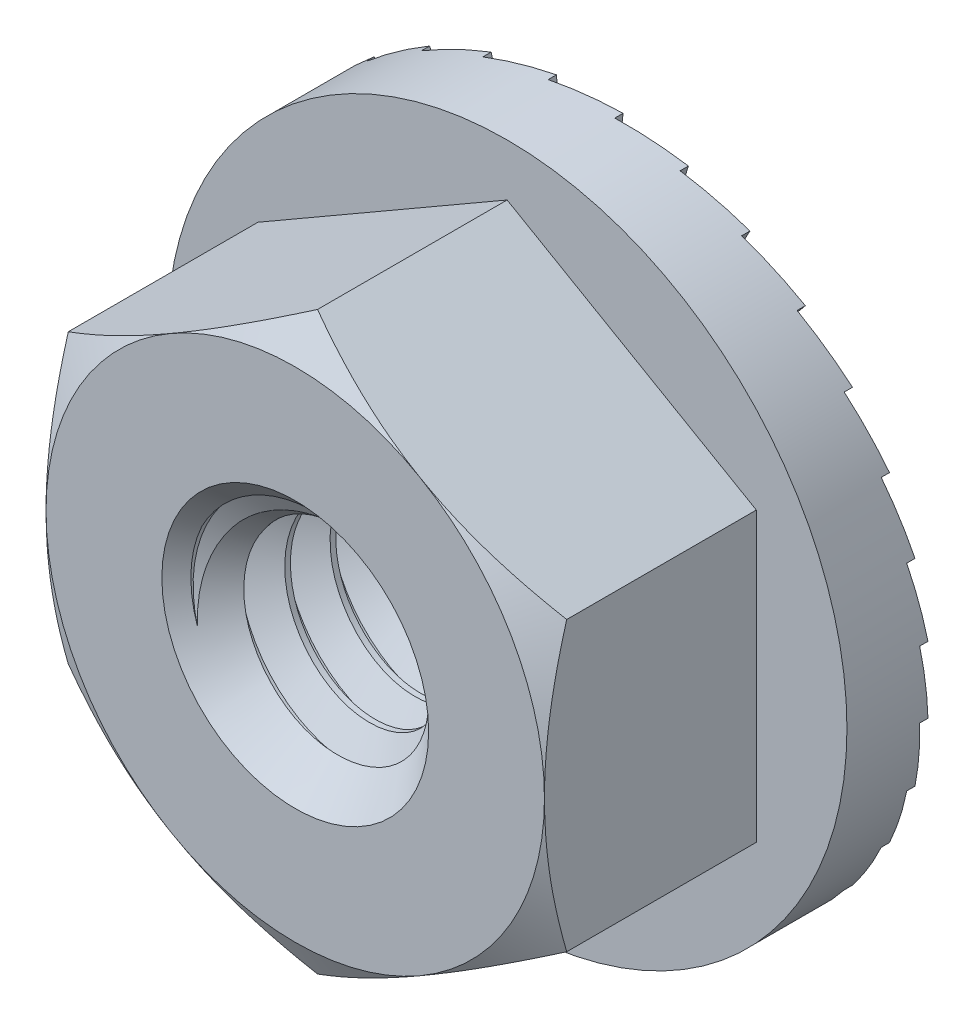
SolidWorks part; units mm, degrees
ref_plane "Front Plane" through (0, 0, 0) normal (0, 0, 1) x (1, 0, 0)
ref_plane "Top Plane" through (0, 0, 0) normal (0, 1, 0) x (1, 0, 0)
ref_plane "Right Plane" through (0, 0, 0) normal (1, 0, 0) x (0, 0, -1)
sketch "Sketch1" plane through (0, 0, 0) normal (0, 0, 1) x (1, 0, 0)
  line L1 (0, 5.041) -> (-4.3656, 2.5205)
  line L2 (-4.3656, 2.5205) -> (-4.3656, -2.5205)
  line L3 (-4.3656, -2.5205) -> (0, -5.041)
  line L4 (0, -5.041) -> (4.3656, -2.5205)
  line L5 (4.3656, -2.5205) -> (4.3656, 2.5205)
  line L6 (4.3656, 2.5205) -> (0, 5.041)
  circle A0 centre (0, 0) radius 4.3656 construction
  dimension "Hex" = 8.7312
extrude "Extrude1" add sketch "Sketch1" against normal blind 5.1594
sketch "Sketch13" plane through (0, 0, -5.1594) normal (0, 0, -1) x (-1, 0, 0)
  circle A0 centre (0, 0) radius 5.9531
  dimension "Flange od" = 11.9062
extrude "Extrude3" add sketch "Sketch13" against normal blind 1.4478
sketch "Sketch2" plane through (0, 0, 0) normal (0, 0, 1) x (1, 0, 0)
  circle A0 centre (0, 0) radius 4.3656 construction
  circle A1 centre (0, 0) radius 4.3656
extrude "Cut-Extrude1" cut sketch "Sketch2" against normal through all draft 60 flip side to cut
sketch "Sketch4" plane through (0, 0, 0) normal (0, 0, 1) x (1, 0, 0)
  circle A0 centre (0, 0) radius 2.0828
  dimension "Thread Dia" = 4.1656
extrude "Cut-Extrude3" cut sketch "Sketch4" against normal through all
sketch "Sketch7" plane through (0, 0, 0) normal (0, 0, 1) x (1, 0, 0)
  circle A4 centre (0, 0) radius 2.3368
  circle A5 centre (0, 0) radius 2.3368
  dimension "D1" = 0.254
sketch "Sketch8" plane through (0, 0, -5.1594) normal (0, 0, -1) x (-1, 0, 0)
  circle A1 centre (0, 0) radius 2.3368
  circle A2 centre (0, 0) radius 2.3368 construction
sketch "Sketch5" plane through (0, 0, 0) normal (0, 0, 1) x (1, 0, 0)
  circle A0 centre (0, 0) radius 2.0828 construction
  circle A1 centre (0, 0) radius 2.0828
curve "Helix/Spiral1" pitch 0.7937 height 5.9531 radius 2.0828 centre (0, 0, 0) axis (0, 0, -1) start towards (0, 1, 0) parameters "pitch"=0.7937
sketch "Sketch9" plane through (0, 0, 0) normal (1, 0, 0) x (0, 0, -1)
  line L0 (-0.3969, 2.0828) -> (-0.2977, 2.0828)
  line L1 (-0.2977, 2.0828) -> (0, 1.5672)
  line L2 (-0.3969, 2.0828) -> (-0.6945, 1.5672)
  line L3 (-0.6945, 1.5672) -> (0, 1.5672)
  line L4 (-0.3473, 2.0828) -> (-0.3473, 1.5672) construction
  line L5 (-0.5457, 1.825) -> (-0.1488, 1.825) construction
  line L7 (0, 1.5672) -> (0, 2.0828) construction
  line L8 (0, 2.0828) -> (0, -2.0828) construction
  dimension "D1" = 0.0992
  dimension "D2" = 0.3969
  dimension "D3" = 60
sketch "Sketch12" plane through (0, 0, 0) normal (0, 0, 1) x (1, 0, 0)
  circle A0 centre (0, 0) radius 1.5672
  circle A1 centre (0, 0) radius 2.0828 construction
  circle A2 centre (0, 0) radius 2.0828
extrude "Extrude2" add sketch "Sketch12" against normal up to surface (5.1594 mm away) up to face at (2.0828, 0, -5.1594)
sweep "Cut-Sweep1" cut profiles "Sketch9" path "Helix/Spiral1" align with end faces yes
extrude "Cut-Extrude6" cut sketch "Sketch7" against normal through all draft 45
extrude "Cut-Extrude7" cut sketch "Sketch8" against normal through all draft 45
sketch "Sketch14" plane through (0, 0, -5.1594) normal (0, 0, -1) x (-1, 0, 0)
  circle A4 centre (0, 0) radius 4.3688
  circle A5 centre (0, 0) radius 4.3688
  dimension "D1" = 2.032
extrude "Cut-Extrude8" cut sketch "Sketch14" against normal blind 0.1448 flip side to cut
sketch "Sketch15" plane through (0, 0, -5.0146) normal (0, 0, -1) x (-1, 0, 0)
  line L0 (-0.4282, 4.3478) -> (-0.5835, 5.9245)
  line L1 (0.4282, 4.3478) -> (0.5835, 5.9245)
  line L2 (0, 0) -> (0.4282, 4.3478) construction
  line L3 (0, 0) -> (-0.4282, 4.3478) construction
  circle A0 centre (0, 0) radius 5.9531 construction
  circle A1 centre (0, 0) radius 4.3688 construction
  arc A2 (0.5835, 5.9245) -> (-0.5835, 5.9245) centre (0, 0) ccw
  arc A3 (0.4282, 4.3478) -> (-0.4282, 4.3478) centre (0, 0) ccw
  dimension "D1" = 11.25
extrude "Extrude4" add sketch "Sketch15" along normal up to surface (0.1448 mm away) separate body up to face at (-2.3368, 0, -5.1594)
sketch "Sketch16" plane through (0, 0, 0) normal (0, 1, 0) x (1, 0, 0)
  line L0 (-0.5835, 5.0146) -> (0.5835, 5.1594)
  line L4 (-0.5835, 5.0146) -> (0.5835, 5.0146)
  line L5 (0.5835, 5.0146) -> (0.5835, 5.1594)
  line L6 (0.5835, 5.1594) -> (-0.5835, 5.1594)
  line L7 (-0.5835, 5.1594) -> (-0.5835, 5.0146)
  line L8 (-0.5835, 5.0146) -> (0.5835, 5.0146) construction
  line L9 (0.5835, 5.0146) -> (0.5835, 5.1594) construction
  line L10 (0.5835, 5.1594) -> (-0.5835, 5.1594)
  line L11 (-0.5835, 5.1594) -> (-0.5835, 5.0146)
  dimension "D1" = 0
extrude "Cut-Extrude9" cut sketch "Sketch16" along normal through all
pattern_circular "CirPattern1" count 32 over 360 about axis through (0, 0, -7.1441) along (0, 0, 1) of bodies 119
combine bodies "Combine1" operation type add bodies to combine 117 119 120 121 122 123 124 125 126 127 128 129 130 131 132 133 134 135 136 137 139 140 141 142 143 144 145 146 147 148 149 150 151
sketch "Sketch17" plane through (0, 0, 0) normal (1, 0, 0) x (0, 0, -1)
  line L0 (5.1594, 5.9531) -> (5.1594, -5.9531) construction
  line L1 (3.7116, 5.9531) -> (3.7116, -5.9531) construction
  dimension "D1" = 1.4478
sketch "Sketch18" plane through (0, 0, -3.7116) normal (0, 0, 1) x (1, 0, 0)
  circle A0 centre (0, 0) radius 5.9531
  circle A1 centre (0, 0) radius 5.9531 construction
equation "\"D2@Sketch9\" = \"pitch@Helix/Spiral1\"*.5"
equation "\"D3@Helix/Spiral1\" = \"pitch@Helix/Spiral1\"+\"Height@Extrude1\""
equation "\"D1@Sketch9\" = \"pitch@Helix/Spiral1\"*.125"
equation "\"D1@Cut-Extrude8\" = \"flange thickness@Extrude3\"*.1"
equation "\"D1@Sketch17\" = \"flange thickness@Extrude3\""
